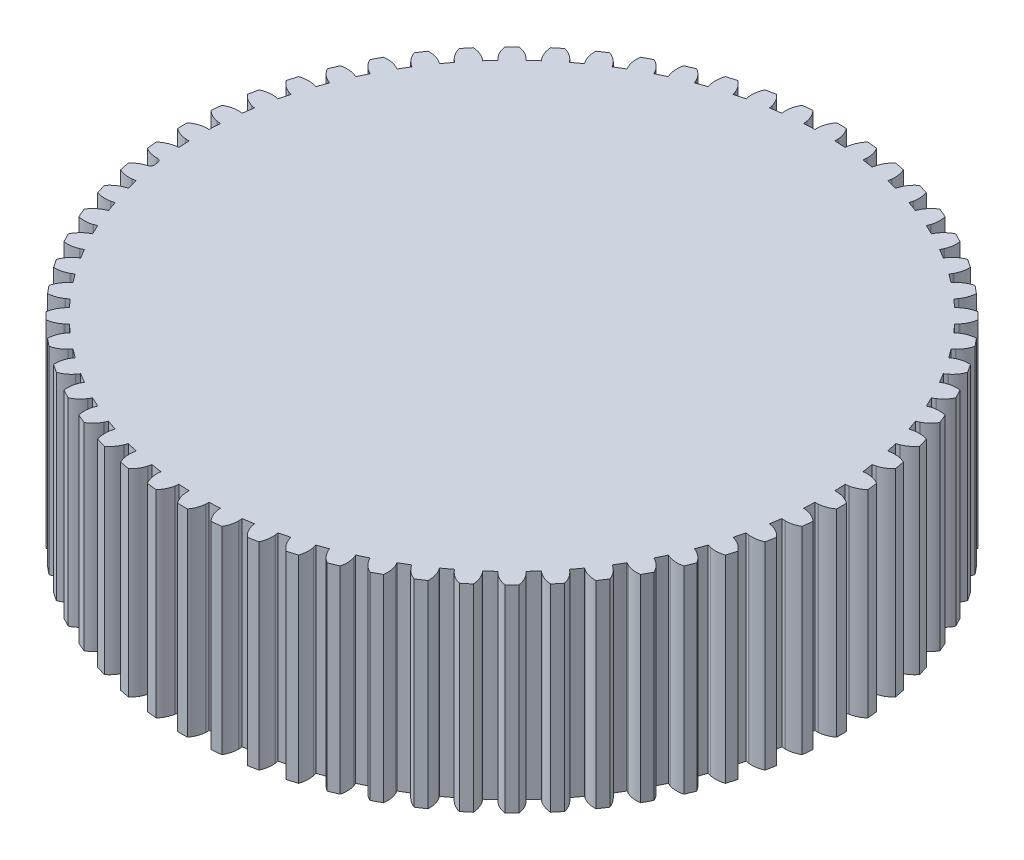
SolidWorks part; units mm, degrees
ref_plane "Front Plane" through (0, 0, 0) normal (0, 0, 1) x (1, 0, 0)
ref_plane "Top Plane" through (0, 0, 0) normal (0, 1, 0) x (1, 0, 0)
ref_plane "Right Plane" through (0, 0, 0) normal (1, 0, 0) x (0, 0, -1)
sketch "Sketch2" plane through (0, 0, 0) normal (0, 1, 0) x (1, 0, 0)
  circle A0 centre (0, 0) radius 47.5
  dimension "D1" = 95
extrude "Boss-Extrude1" add sketch "Sketch2" along normal blind 30
sketch "Sketch3" plane through (0, 30, 0) normal (0, 1, 0) x (1, 0, 0)
  line L0 (0, 0) -> (0, 58.33) construction
  line L1 (-0.75, 49.9944) -> (0.75, 49.9944)
  line L2 (4.1539, 49.8272) -> (5.6467, 49.6801)
  line L3 (9.0178, 49.1801) -> (10.489, 48.8874)
  line L4 (13.7949, 48.0593) -> (15.2303, 47.6239)
  line L5 (18.4391, 46.4758) -> (19.8249, 45.9018)
  line L6 (22.9057, 44.4446) -> (24.2286, 43.7376)
  line L7 (27.1518, 41.9855) -> (28.399, 41.1521)
  line L8 (31.1363, 39.122) -> (32.2959, 38.1704)
  line L9 (34.821, 35.8817) -> (35.8817, 34.821)
  line L10 (38.1704, 32.2959) -> (39.122, 31.1363)
  line L11 (41.1521, 28.399) -> (41.9855, 27.1518)
  line L12 (43.7376, 24.2286) -> (44.4446, 22.9057)
  line L13 (45.9018, 19.8249) -> (46.4758, 18.4391)
  line L14 (47.6239, 15.2303) -> (48.0593, 13.7949)
  line L15 (48.8874, 10.489) -> (49.1801, 9.0178)
  line L16 (49.6801, 5.6467) -> (49.8272, 4.1539)
  line L17 (49.9944, 0.75) -> (49.9944, -0.75)
  line L18 (49.8272, -4.1539) -> (49.6801, -5.6467)
  line L19 (49.1801, -9.0178) -> (48.8874, -10.489)
  line L20 (48.0593, -13.7949) -> (47.6239, -15.2303)
  line L21 (46.4758, -18.4391) -> (45.9018, -19.8249)
  line L22 (44.4446, -22.9057) -> (43.7376, -24.2286)
  line L23 (41.9855, -27.1518) -> (41.1521, -28.399)
  line L24 (39.122, -31.1363) -> (38.1704, -32.2959)
  line L25 (35.8817, -34.821) -> (34.821, -35.8817)
  line L26 (32.2959, -38.1704) -> (31.1363, -39.122)
  line L27 (28.399, -41.1521) -> (27.1518, -41.9855)
  line L28 (24.2286, -43.7376) -> (22.9057, -44.4446)
  line L29 (19.8249, -45.9018) -> (18.4391, -46.4758)
  line L30 (15.2303, -47.6239) -> (13.7949, -48.0593)
  line L31 (10.489, -48.8874) -> (9.0178, -49.1801)
  line L32 (5.6467, -49.6801) -> (4.1539, -49.8272)
  line L33 (0.75, -49.9944) -> (-0.75, -49.9944)
  line L34 (-4.1539, -49.8272) -> (-5.6467, -49.6801)
  line L35 (-9.0178, -49.1801) -> (-10.489, -48.8874)
  line L36 (-13.7949, -48.0593) -> (-15.2303, -47.6239)
  line L37 (-18.4391, -46.4758) -> (-19.8249, -45.9018)
  line L38 (-22.9057, -44.4446) -> (-24.2286, -43.7376)
  line L39 (-27.1518, -41.9855) -> (-28.399, -41.1521)
  line L40 (-31.1363, -39.122) -> (-32.2959, -38.1704)
  line L41 (-34.821, -35.8817) -> (-35.8817, -34.821)
  line L42 (-38.1704, -32.2959) -> (-39.122, -31.1363)
  line L43 (-41.1521, -28.399) -> (-41.9855, -27.1518)
  line L44 (-43.7376, -24.2286) -> (-44.4446, -22.9057)
  line L45 (-45.9018, -19.8249) -> (-46.4758, -18.4391)
  line L46 (-47.6239, -15.2303) -> (-48.0593, -13.7949)
  line L47 (-48.8874, -10.489) -> (-49.1801, -9.0178)
  line L48 (-49.6801, -5.6467) -> (-49.8272, -4.1539)
  line L49 (-49.9944, -0.75) -> (-49.9944, 0.75)
  line L50 (-49.8272, 4.1539) -> (-49.6801, 5.6467)
  line L51 (-49.1801, 9.0178) -> (-48.8874, 10.489)
  line L52 (-48.0593, 13.7949) -> (-47.6239, 15.2303)
  line L53 (-46.4758, 18.4391) -> (-45.9018, 19.8249)
  line L54 (-44.4446, 22.9057) -> (-43.7376, 24.2286)
  line L55 (-41.9855, 27.1518) -> (-41.1521, 28.399)
  line L56 (-39.122, 31.1363) -> (-38.1704, 32.2959)
  line L57 (-35.8817, 34.821) -> (-34.821, 35.8817)
  line L58 (-32.2959, 38.1704) -> (-31.1363, 39.122)
  line L59 (-28.399, 41.1521) -> (-27.1518, 41.9855)
  line L60 (-24.2286, 43.7376) -> (-22.9057, 44.4446)
  line L61 (-19.8249, 45.9018) -> (-18.4391, 46.4758)
  line L62 (-15.2303, 47.6239) -> (-13.7949, 48.0593)
  line L63 (-10.489, 48.8874) -> (-9.0178, 49.1801)
  line L64 (-5.6467, 49.6801) -> (-4.1539, 49.8272)
  circle A0 centre (0, 0) radius 50
  arc A1 (-1.5, 47.3756) -> (-0.75, 49.9944) centre (2.2906, 47.7068) cw
  arc A2 (-2.1047, 47.4533) -> (-1.5, 48.038) centre (-2.0947, 48.048) ccw
  arc A3 (2.1047, 47.4533) -> (1.5, 48.038) centre (2.0947, 48.048) cw
  circle A4 centre (0, 0) radius 47.5 construction
  arc A5 (1.5, 47.3756) -> (0.75, 49.9944) centre (-2.2906, 47.7068) ccw
  arc A6 (3.1508, 47.2945) -> (4.1539, 49.8272) centre (6.9557, 47.2525) cw
  arc A7 (2.5567, 47.4311) -> (3.2158, 47.9537) centre (2.6249, 48.022) ccw
  arc A8 (6.1364, 47.0004) -> (5.6467, 49.6801) centre (2.3965, 47.7016) ccw
  arc A9 (6.7458, 47.0185) -> (6.2013, 47.6596) centre (6.7941, 47.6113) cw
  arc A10 (7.7713, 46.7579) -> (9.0178, 49.1801) centre (11.5537, 46.3432) cw
  arc A11 (7.1934, 46.9522) -> (7.9006, 47.4076) centre (7.3193, 47.5334) ccw
  arc A12 (10.7137, 46.1726) -> (10.489, 48.8874) centre (7.0605, 47.237) ccw
  arc A13 (11.322, 46.1309) -> (10.8429, 46.8223) centre (11.4281, 46.7161) cw
  arc A14 (12.317, 45.771) -> (13.7949, 48.0593) centre (16.0405, 44.9876) cw
  arc A15 (11.7609, 46.021) -> (12.5093, 46.4049) centre (11.9431, 46.5871) ccw
  arc A16 (15.1878, 44.9002) -> (15.2303, 47.6239) centre (11.6566, 46.3175) ccw
  arc A17 (15.7891, 44.7991) -> (15.3801, 45.534) centre (15.9521, 45.371) cw
  arc A18 (16.744, 44.3434) -> (18.4391, 46.4758) centre (20.3729, 43.1987) cw
  arc A19 (16.2151, 44.6466) -> (16.9975, 44.9553) centre (16.452, 45.1922) ccw
  arc A20 (19.5157, 43.1953) -> (19.8249, 45.9018) centre (16.1403, 44.9519) ccw
  arc A21 (20.1041, 43.0357) -> (19.7692, 43.8073) centre (20.3224, 43.589) cw
  arc A22 (21.0098, 42.4886) -> (22.9057, 44.4446) centre (24.509, 40.9938) cw
  arc A23 (20.5132, 42.8423) -> (21.3221, 43.0728) centre (20.8023, 43.362) ccw
  arc A24 (23.6556, 41.0744) -> (24.2286, 43.7376) centre (20.4687, 43.1534) ccw
  arc A25 (24.2256, 40.858) -> (23.9678, 41.6586) centre (24.497, 41.3871) cw
  arc A26 (25.0733, 40.2247) -> (27.1518, 41.9855) centre (28.409, 38.3941) cw
  arc A27 (24.6137, 40.6253) -> (25.4413, 40.7755) centre (24.9524, 41.1142) ccw
  arc A28 (27.5677, 38.558) -> (28.399, 41.1521) centre (24.5999, 40.9393) ccw
  arc A29 (28.1137, 38.2867) -> (27.9357, 39.1087) centre (28.4357, 38.7867) cw
  arc A30 (28.8952, 37.5734) -> (31.1363, 39.122) centre (32.0355, 35.4247) cw
  arc A31 (28.4771, 38.0172) -> (29.3154, 38.0854) centre (28.8621, 38.4705) ccw
  arc A32 (31.2143, 35.6702) -> (32.2959, 38.1704) centre (28.4942, 38.331) ccw
  arc A33 (31.7311, 35.3467) -> (31.6345, 36.1823) centre (32.1005, 35.8128) cw
  arc A34 (32.4389, 34.5603) -> (34.821, 35.8817) centre (35.3535, 32.1141) cw
  arc A35 (32.0663, 35.0428) -> (32.9073, 35.0286) centre (32.4939, 35.4562) ccw
  arc A36 (34.5603, 32.4389) -> (35.8817, 34.821) centre (32.1141, 35.3535) ccw
  arc A37 (35.0428, 32.0663) -> (35.0286, 32.9073) centre (35.4562, 32.4939) cw
  arc A38 (35.6702, 31.2143) -> (38.1704, 32.2959) centre (38.331, 28.4942) cw
  arc A39 (35.3467, 31.7311) -> (36.1823, 31.6345) centre (35.8128, 32.1005) ccw
  arc A40 (37.5734, 28.8952) -> (39.122, 31.1363) centre (35.4247, 32.0355) ccw
  arc A41 (38.0172, 28.4771) -> (38.0854, 29.3154) centre (38.4705, 28.8621) cw
  arc A42 (38.558, 27.5677) -> (41.1521, 28.399) centre (40.9393, 24.5999) cw
  arc A43 (38.2867, 28.1137) -> (39.1087, 27.9357) centre (38.7867, 28.4357) ccw
  arc A44 (40.2247, 25.0733) -> (41.9855, 27.1518) centre (38.3941, 28.409) ccw
  arc A45 (40.6253, 24.6137) -> (40.7755, 25.4413) centre (41.1142, 24.9524) cw
  arc A46 (41.0744, 23.6556) -> (43.7376, 24.2286) centre (43.1534, 20.4687) cw
  arc A47 (40.858, 24.2256) -> (41.6586, 23.9678) centre (41.3871, 24.497) ccw
  arc A48 (42.4886, 21.0098) -> (44.4446, 22.9057) centre (40.9938, 24.509) ccw
  arc A49 (42.8423, 20.5132) -> (43.0728, 21.3221) centre (43.362, 20.8023) cw
  arc A50 (43.1953, 19.5157) -> (45.9018, 19.8249) centre (44.9519, 16.1403) cw
  arc A51 (43.0357, 20.1041) -> (43.8073, 19.7692) centre (43.589, 20.3224) ccw
  arc A52 (44.3434, 16.744) -> (46.4758, 18.4391) centre (43.1987, 20.3729) ccw
  arc A53 (44.6466, 16.2151) -> (44.9553, 16.9975) centre (45.1922, 16.452) cw
  arc A54 (44.9002, 15.1878) -> (47.6239, 15.2303) centre (46.3175, 11.6566) cw
  arc A55 (44.7991, 15.7891) -> (45.534, 15.3801) centre (45.371, 15.9521) ccw
  arc A56 (45.771, 12.317) -> (48.0593, 13.7949) centre (44.9876, 16.0405) ccw
  arc A57 (46.021, 11.7609) -> (46.4049, 12.5093) centre (46.5871, 11.9431) cw
  arc A58 (46.1726, 10.7137) -> (48.8874, 10.489) centre (47.237, 7.0605) cw
  arc A59 (46.1309, 11.322) -> (46.8223, 10.8429) centre (46.7161, 11.4281) ccw
  arc A60 (46.7579, 7.7713) -> (49.1801, 9.0178) centre (46.3432, 11.5537) ccw
  arc A61 (46.9522, 7.1934) -> (47.4076, 7.9006) centre (47.5334, 7.3193) cw
  arc A62 (47.0004, 6.1364) -> (49.6801, 5.6467) centre (47.7016, 2.3965) cw
  arc A63 (47.0185, 6.7458) -> (47.6596, 6.2013) centre (47.6113, 6.7941) ccw
  arc A64 (47.2945, 3.1508) -> (49.8272, 4.1539) centre (47.2525, 6.9557) ccw
  arc A65 (47.4311, 2.5567) -> (47.9537, 3.2158) centre (48.022, 2.6249) cw
  arc A66 (47.3756, 1.5) -> (49.9944, 0.75) centre (47.7068, -2.2906) cw
  arc A67 (47.4533, 2.1047) -> (48.038, 1.5) centre (48.048, 2.0947) ccw
  arc A68 (47.3756, -1.5) -> (49.9944, -0.75) centre (47.7068, 2.2906) ccw
  arc A69 (47.4533, -2.1047) -> (48.038, -1.5) centre (48.048, -2.0947) cw
  arc A70 (47.2945, -3.1508) -> (49.8272, -4.1539) centre (47.2525, -6.9557) cw
  arc A71 (47.4311, -2.5567) -> (47.9537, -3.2158) centre (48.022, -2.6249) ccw
  arc A72 (47.0004, -6.1364) -> (49.6801, -5.6467) centre (47.7016, -2.3965) ccw
  arc A73 (47.0185, -6.7458) -> (47.6596, -6.2013) centre (47.6113, -6.7941) cw
  arc A74 (46.7579, -7.7713) -> (49.1801, -9.0178) centre (46.3432, -11.5537) cw
  arc A75 (46.9522, -7.1934) -> (47.4076, -7.9006) centre (47.5334, -7.3193) ccw
  arc A76 (46.1726, -10.7137) -> (48.8874, -10.489) centre (47.237, -7.0605) ccw
  arc A77 (46.1309, -11.322) -> (46.8223, -10.8429) centre (46.7161, -11.4281) cw
  arc A78 (45.771, -12.317) -> (48.0593, -13.7949) centre (44.9876, -16.0405) cw
  arc A79 (46.021, -11.7609) -> (46.4049, -12.5093) centre (46.5871, -11.9431) ccw
  arc A80 (44.9002, -15.1878) -> (47.6239, -15.2303) centre (46.3175, -11.6566) ccw
  arc A81 (44.7991, -15.7891) -> (45.534, -15.3801) centre (45.371, -15.9521) cw
  arc A82 (44.3434, -16.744) -> (46.4758, -18.4391) centre (43.1987, -20.3729) cw
  arc A83 (44.6466, -16.2151) -> (44.9553, -16.9975) centre (45.1922, -16.452) ccw
  arc A84 (43.1953, -19.5157) -> (45.9018, -19.8249) centre (44.9519, -16.1403) ccw
  arc A85 (43.0357, -20.1041) -> (43.8073, -19.7692) centre (43.589, -20.3224) cw
  arc A86 (42.4886, -21.0098) -> (44.4446, -22.9057) centre (40.9938, -24.509) cw
  arc A87 (42.8423, -20.5132) -> (43.0728, -21.3221) centre (43.362, -20.8023) ccw
  arc A88 (41.0744, -23.6556) -> (43.7376, -24.2286) centre (43.1534, -20.4687) ccw
  arc A89 (40.858, -24.2256) -> (41.6586, -23.9678) centre (41.3871, -24.497) cw
  arc A90 (40.2247, -25.0733) -> (41.9855, -27.1518) centre (38.3941, -28.409) cw
  arc A91 (40.6253, -24.6137) -> (40.7755, -25.4413) centre (41.1142, -24.9524) ccw
  arc A92 (38.558, -27.5677) -> (41.1521, -28.399) centre (40.9393, -24.5999) ccw
  arc A93 (38.2867, -28.1137) -> (39.1087, -27.9357) centre (38.7867, -28.4357) cw
  arc A94 (37.5734, -28.8952) -> (39.122, -31.1363) centre (35.4247, -32.0355) cw
  arc A95 (38.0172, -28.4771) -> (38.0854, -29.3154) centre (38.4705, -28.8621) ccw
  arc A96 (35.6702, -31.2143) -> (38.1704, -32.2959) centre (38.331, -28.4942) ccw
  arc A97 (35.3467, -31.7311) -> (36.1823, -31.6345) centre (35.8128, -32.1005) cw
  arc A98 (34.5603, -32.4389) -> (35.8817, -34.821) centre (32.1141, -35.3535) cw
  arc A99 (35.0428, -32.0663) -> (35.0286, -32.9073) centre (35.4562, -32.4939) ccw
  arc A100 (32.4389, -34.5603) -> (34.821, -35.8817) centre (35.3535, -32.1141) ccw
  arc A101 (32.0663, -35.0428) -> (32.9073, -35.0286) centre (32.4939, -35.4562) cw
  arc A102 (31.2143, -35.6702) -> (32.2959, -38.1704) centre (28.4942, -38.331) cw
  arc A103 (31.7311, -35.3467) -> (31.6345, -36.1823) centre (32.1005, -35.8128) ccw
  arc A104 (28.8952, -37.5734) -> (31.1363, -39.122) centre (32.0355, -35.4247) ccw
  arc A105 (28.4771, -38.0172) -> (29.3154, -38.0854) centre (28.8621, -38.4705) cw
  arc A106 (27.5677, -38.558) -> (28.399, -41.1521) centre (24.5999, -40.9393) cw
  arc A107 (28.1137, -38.2867) -> (27.9357, -39.1087) centre (28.4357, -38.7867) ccw
  arc A108 (25.0733, -40.2247) -> (27.1518, -41.9855) centre (28.409, -38.3941) ccw
  arc A109 (24.6137, -40.6253) -> (25.4413, -40.7755) centre (24.9524, -41.1142) cw
  arc A110 (23.6556, -41.0744) -> (24.2286, -43.7376) centre (20.4687, -43.1534) cw
  arc A111 (24.2256, -40.858) -> (23.9678, -41.6586) centre (24.497, -41.3871) ccw
  arc A112 (21.0098, -42.4886) -> (22.9057, -44.4446) centre (24.509, -40.9938) ccw
  arc A113 (20.5132, -42.8423) -> (21.3221, -43.0728) centre (20.8023, -43.362) cw
  arc A114 (19.5157, -43.1953) -> (19.8249, -45.9018) centre (16.1403, -44.9519) cw
  arc A115 (20.1041, -43.0357) -> (19.7692, -43.8073) centre (20.3224, -43.589) ccw
  arc A116 (16.744, -44.3434) -> (18.4391, -46.4758) centre (20.3729, -43.1987) ccw
  arc A117 (16.2151, -44.6466) -> (16.9975, -44.9553) centre (16.452, -45.1922) cw
  arc A118 (15.1878, -44.9002) -> (15.2303, -47.6239) centre (11.6566, -46.3175) cw
  arc A119 (15.7891, -44.7991) -> (15.3801, -45.534) centre (15.9521, -45.371) ccw
  arc A120 (12.317, -45.771) -> (13.7949, -48.0593) centre (16.0405, -44.9876) ccw
  arc A121 (11.7609, -46.021) -> (12.5093, -46.4049) centre (11.9431, -46.5871) cw
  arc A122 (10.7137, -46.1726) -> (10.489, -48.8874) centre (7.0605, -47.237) cw
  arc A123 (11.322, -46.1309) -> (10.8429, -46.8223) centre (11.4281, -46.7161) ccw
  arc A124 (7.7713, -46.7579) -> (9.0178, -49.1801) centre (11.5537, -46.3432) ccw
  arc A125 (7.1934, -46.9522) -> (7.9006, -47.4076) centre (7.3193, -47.5334) cw
  arc A126 (6.1364, -47.0004) -> (5.6467, -49.6801) centre (2.3965, -47.7016) cw
  arc A127 (6.7458, -47.0185) -> (6.2013, -47.6596) centre (6.7941, -47.6113) ccw
  arc A128 (3.1508, -47.2945) -> (4.1539, -49.8272) centre (6.9557, -47.2525) ccw
  arc A129 (2.5567, -47.4311) -> (3.2158, -47.9537) centre (2.6249, -48.022) cw
  arc A130 (1.5, -47.3756) -> (0.75, -49.9944) centre (-2.2906, -47.7068) cw
  arc A131 (2.1047, -47.4533) -> (1.5, -48.038) centre (2.0947, -48.048) ccw
  arc A132 (-1.5, -47.3756) -> (-0.75, -49.9944) centre (2.2906, -47.7068) ccw
  arc A133 (-2.1047, -47.4533) -> (-1.5, -48.038) centre (-2.0947, -48.048) cw
  arc A134 (-3.1508, -47.2945) -> (-4.1539, -49.8272) centre (-6.9557, -47.2525) cw
  arc A135 (-2.5567, -47.4311) -> (-3.2158, -47.9537) centre (-2.6249, -48.022) ccw
  arc A136 (-6.1364, -47.0004) -> (-5.6467, -49.6801) centre (-2.3965, -47.7016) ccw
  arc A137 (-6.7458, -47.0185) -> (-6.2013, -47.6596) centre (-6.7941, -47.6113) cw
  arc A138 (-7.7713, -46.7579) -> (-9.0178, -49.1801) centre (-11.5537, -46.3432) cw
  arc A139 (-7.1934, -46.9522) -> (-7.9006, -47.4076) centre (-7.3193, -47.5334) ccw
  arc A140 (-10.7137, -46.1726) -> (-10.489, -48.8874) centre (-7.0605, -47.237) ccw
  arc A141 (-11.322, -46.1309) -> (-10.8429, -46.8223) centre (-11.4281, -46.7161) cw
  arc A142 (-12.317, -45.771) -> (-13.7949, -48.0593) centre (-16.0405, -44.9876) cw
  arc A143 (-11.7609, -46.021) -> (-12.5093, -46.4049) centre (-11.9431, -46.5871) ccw
  arc A144 (-15.1878, -44.9002) -> (-15.2303, -47.6239) centre (-11.6566, -46.3175) ccw
  arc A145 (-15.7891, -44.7991) -> (-15.3801, -45.534) centre (-15.9521, -45.371) cw
  arc A146 (-16.744, -44.3434) -> (-18.4391, -46.4758) centre (-20.3729, -43.1987) cw
  arc A147 (-16.2151, -44.6466) -> (-16.9975, -44.9553) centre (-16.452, -45.1922) ccw
  arc A148 (-19.5157, -43.1953) -> (-19.8249, -45.9018) centre (-16.1403, -44.9519) ccw
  arc A149 (-20.1041, -43.0357) -> (-19.7692, -43.8073) centre (-20.3224, -43.589) cw
  arc A150 (-21.0098, -42.4886) -> (-22.9057, -44.4446) centre (-24.509, -40.9938) cw
  arc A151 (-20.5132, -42.8423) -> (-21.3221, -43.0728) centre (-20.8023, -43.362) ccw
  arc A152 (-23.6556, -41.0744) -> (-24.2286, -43.7376) centre (-20.4687, -43.1534) ccw
  arc A153 (-24.2256, -40.858) -> (-23.9678, -41.6586) centre (-24.497, -41.3871) cw
  arc A154 (-25.0733, -40.2247) -> (-27.1518, -41.9855) centre (-28.409, -38.3941) cw
  arc A155 (-24.6137, -40.6253) -> (-25.4413, -40.7755) centre (-24.9524, -41.1142) ccw
  arc A156 (-27.5677, -38.558) -> (-28.399, -41.1521) centre (-24.5999, -40.9393) ccw
  arc A157 (-28.1137, -38.2867) -> (-27.9357, -39.1087) centre (-28.4357, -38.7867) cw
  arc A158 (-28.8952, -37.5734) -> (-31.1363, -39.122) centre (-32.0355, -35.4247) cw
  arc A159 (-28.4771, -38.0172) -> (-29.3154, -38.0854) centre (-28.8621, -38.4705) ccw
  arc A160 (-31.2143, -35.6702) -> (-32.2959, -38.1704) centre (-28.4942, -38.331) ccw
  arc A161 (-31.7311, -35.3467) -> (-31.6345, -36.1823) centre (-32.1005, -35.8128) cw
  arc A162 (-32.4389, -34.5603) -> (-34.821, -35.8817) centre (-35.3535, -32.1141) cw
  arc A163 (-32.0663, -35.0428) -> (-32.9073, -35.0286) centre (-32.4939, -35.4562) ccw
  arc A164 (-34.5603, -32.4389) -> (-35.8817, -34.821) centre (-32.1141, -35.3535) ccw
  arc A165 (-35.0428, -32.0663) -> (-35.0286, -32.9073) centre (-35.4562, -32.4939) cw
  arc A166 (-35.6702, -31.2143) -> (-38.1704, -32.2959) centre (-38.331, -28.4942) cw
  arc A167 (-35.3467, -31.7311) -> (-36.1823, -31.6345) centre (-35.8128, -32.1005) ccw
  arc A168 (-37.5734, -28.8952) -> (-39.122, -31.1363) centre (-35.4247, -32.0355) ccw
  arc A169 (-38.0172, -28.4771) -> (-38.0854, -29.3154) centre (-38.4705, -28.8621) cw
  arc A170 (-38.558, -27.5677) -> (-41.1521, -28.399) centre (-40.9393, -24.5999) cw
  arc A171 (-38.2867, -28.1137) -> (-39.1087, -27.9357) centre (-38.7867, -28.4357) ccw
  arc A172 (-40.2247, -25.0733) -> (-41.9855, -27.1518) centre (-38.3941, -28.409) ccw
  arc A173 (-40.6253, -24.6137) -> (-40.7755, -25.4413) centre (-41.1142, -24.9524) cw
  arc A174 (-41.0744, -23.6556) -> (-43.7376, -24.2286) centre (-43.1534, -20.4687) cw
  arc A175 (-40.858, -24.2256) -> (-41.6586, -23.9678) centre (-41.3871, -24.497) ccw
  arc A176 (-42.4886, -21.0098) -> (-44.4446, -22.9057) centre (-40.9938, -24.509) ccw
  arc A177 (-42.8423, -20.5132) -> (-43.0728, -21.3221) centre (-43.362, -20.8023) cw
  arc A178 (-43.1953, -19.5157) -> (-45.9018, -19.8249) centre (-44.9519, -16.1403) cw
  arc A179 (-43.0357, -20.1041) -> (-43.8073, -19.7692) centre (-43.589, -20.3224) ccw
  arc A180 (-44.3434, -16.744) -> (-46.4758, -18.4391) centre (-43.1987, -20.3729) ccw
  arc A181 (-44.6466, -16.2151) -> (-44.9553, -16.9975) centre (-45.1922, -16.452) cw
  arc A182 (-44.9002, -15.1878) -> (-47.6239, -15.2303) centre (-46.3175, -11.6566) cw
  arc A183 (-44.7991, -15.7891) -> (-45.534, -15.3801) centre (-45.371, -15.9521) ccw
  arc A184 (-45.771, -12.317) -> (-48.0593, -13.7949) centre (-44.9876, -16.0405) ccw
  arc A185 (-46.021, -11.7609) -> (-46.4049, -12.5093) centre (-46.5871, -11.9431) cw
  arc A186 (-46.1726, -10.7137) -> (-48.8874, -10.489) centre (-47.237, -7.0605) cw
  arc A187 (-46.1309, -11.322) -> (-46.8223, -10.8429) centre (-46.7161, -11.4281) ccw
  arc A188 (-46.7579, -7.7713) -> (-49.1801, -9.0178) centre (-46.3432, -11.5537) ccw
  arc A189 (-46.9522, -7.1934) -> (-47.4076, -7.9006) centre (-47.5334, -7.3193) cw
  arc A190 (-47.0004, -6.1364) -> (-49.6801, -5.6467) centre (-47.7016, -2.3965) cw
  arc A191 (-47.0185, -6.7458) -> (-47.6596, -6.2013) centre (-47.6113, -6.7941) ccw
  arc A192 (-47.2945, -3.1508) -> (-49.8272, -4.1539) centre (-47.2525, -6.9557) ccw
  arc A193 (-47.4311, -2.5567) -> (-47.9537, -3.2158) centre (-48.022, -2.6249) cw
  arc A194 (-47.3756, -1.5) -> (-49.9944, -0.75) centre (-47.7068, 2.2906) cw
  arc A195 (-47.4533, -2.1047) -> (-48.038, -1.5) centre (-48.048, -2.0947) ccw
  arc A196 (-47.3756, 1.5) -> (-49.9944, 0.75) centre (-47.7068, -2.2906) ccw
  arc A197 (-47.4533, 2.1047) -> (-48.038, 1.5) centre (-48.048, 2.0947) cw
  arc A198 (-47.2945, 3.1508) -> (-49.8272, 4.1539) centre (-47.2525, 6.9557) cw
  arc A199 (-47.4311, 2.5567) -> (-47.9537, 3.2158) centre (-48.022, 2.6249) ccw
  arc A200 (-47.0004, 6.1364) -> (-49.6801, 5.6467) centre (-47.7016, 2.3965) ccw
  arc A201 (-47.0185, 6.7458) -> (-47.6596, 6.2013) centre (-47.6113, 6.7941) cw
  arc A202 (-46.7579, 7.7713) -> (-49.1801, 9.0178) centre (-46.3432, 11.5537) cw
  arc A203 (-46.9522, 7.1934) -> (-47.4076, 7.9006) centre (-47.5334, 7.3193) ccw
  arc A204 (-46.1726, 10.7137) -> (-48.8874, 10.489) centre (-47.237, 7.0605) ccw
  arc A205 (-46.1309, 11.322) -> (-46.8223, 10.8429) centre (-46.7161, 11.4281) cw
  arc A206 (-45.771, 12.317) -> (-48.0593, 13.7949) centre (-44.9876, 16.0405) cw
  arc A207 (-46.021, 11.7609) -> (-46.4049, 12.5093) centre (-46.5871, 11.9431) ccw
  arc A208 (-44.9002, 15.1878) -> (-47.6239, 15.2303) centre (-46.3175, 11.6566) ccw
  arc A209 (-44.7991, 15.7891) -> (-45.534, 15.3801) centre (-45.371, 15.9521) cw
  arc A210 (-44.3434, 16.744) -> (-46.4758, 18.4391) centre (-43.1987, 20.3729) cw
  arc A211 (-44.6466, 16.2151) -> (-44.9553, 16.9975) centre (-45.1922, 16.452) ccw
  arc A212 (-43.1953, 19.5157) -> (-45.9018, 19.8249) centre (-44.9519, 16.1403) ccw
  arc A213 (-43.0357, 20.1041) -> (-43.8073, 19.7692) centre (-43.589, 20.3224) cw
  arc A214 (-42.4886, 21.0098) -> (-44.4446, 22.9057) centre (-40.9938, 24.509) cw
  arc A215 (-42.8423, 20.5132) -> (-43.0728, 21.3221) centre (-43.362, 20.8023) ccw
  arc A216 (-41.0744, 23.6556) -> (-43.7376, 24.2286) centre (-43.1534, 20.4687) ccw
  arc A217 (-40.858, 24.2256) -> (-41.6586, 23.9678) centre (-41.3871, 24.497) cw
  arc A218 (-40.2247, 25.0733) -> (-41.9855, 27.1518) centre (-38.3941, 28.409) cw
  arc A219 (-40.6253, 24.6137) -> (-40.7755, 25.4413) centre (-41.1142, 24.9524) ccw
  arc A220 (-38.558, 27.5677) -> (-41.1521, 28.399) centre (-40.9393, 24.5999) ccw
  arc A221 (-38.2867, 28.1137) -> (-39.1087, 27.9357) centre (-38.7867, 28.4357) cw
  arc A222 (-37.5734, 28.8952) -> (-39.122, 31.1363) centre (-35.4247, 32.0355) cw
  arc A223 (-38.0172, 28.4771) -> (-38.0854, 29.3154) centre (-38.4705, 28.8621) ccw
  arc A224 (-35.6702, 31.2143) -> (-38.1704, 32.2959) centre (-38.331, 28.4942) ccw
  arc A225 (-35.3467, 31.7311) -> (-36.1823, 31.6345) centre (-35.8128, 32.1005) cw
  arc A226 (-34.5603, 32.4389) -> (-35.8817, 34.821) centre (-32.1141, 35.3535) cw
  arc A227 (-35.0428, 32.0663) -> (-35.0286, 32.9073) centre (-35.4562, 32.4939) ccw
  arc A228 (-32.4389, 34.5603) -> (-34.821, 35.8817) centre (-35.3535, 32.1141) ccw
  arc A229 (-32.0663, 35.0428) -> (-32.9073, 35.0286) centre (-32.4939, 35.4562) cw
  arc A230 (-31.2143, 35.6702) -> (-32.2959, 38.1704) centre (-28.4942, 38.331) cw
  arc A231 (-31.7311, 35.3467) -> (-31.6345, 36.1823) centre (-32.1005, 35.8128) ccw
  arc A232 (-28.8952, 37.5734) -> (-31.1363, 39.122) centre (-32.0355, 35.4247) ccw
  arc A233 (-28.4771, 38.0172) -> (-29.3154, 38.0854) centre (-28.8621, 38.4705) cw
  arc A234 (-27.5677, 38.558) -> (-28.399, 41.1521) centre (-24.5999, 40.9393) cw
  arc A235 (-28.1137, 38.2867) -> (-27.9357, 39.1087) centre (-28.4357, 38.7867) ccw
  arc A236 (-25.0733, 40.2247) -> (-27.1518, 41.9855) centre (-28.409, 38.3941) ccw
  arc A237 (-24.6137, 40.6253) -> (-25.4413, 40.7755) centre (-24.9524, 41.1142) cw
  arc A238 (-23.6556, 41.0744) -> (-24.2286, 43.7376) centre (-20.4687, 43.1534) cw
  arc A239 (-24.2256, 40.858) -> (-23.9678, 41.6586) centre (-24.497, 41.3871) ccw
  arc A240 (-21.0098, 42.4886) -> (-22.9057, 44.4446) centre (-24.509, 40.9938) ccw
  arc A241 (-20.5132, 42.8423) -> (-21.3221, 43.0728) centre (-20.8023, 43.362) cw
  arc A242 (-19.5157, 43.1953) -> (-19.8249, 45.9018) centre (-16.1403, 44.9519) cw
  arc A243 (-20.1041, 43.0357) -> (-19.7692, 43.8073) centre (-20.3224, 43.589) ccw
  arc A244 (-16.744, 44.3434) -> (-18.4391, 46.4758) centre (-20.3729, 43.1987) ccw
  arc A245 (-16.2151, 44.6466) -> (-16.9975, 44.9553) centre (-16.452, 45.1922) cw
  arc A246 (-15.1878, 44.9002) -> (-15.2303, 47.6239) centre (-11.6566, 46.3175) cw
  arc A247 (-15.7891, 44.7991) -> (-15.3801, 45.534) centre (-15.9521, 45.371) ccw
  arc A248 (-12.317, 45.771) -> (-13.7949, 48.0593) centre (-16.0405, 44.9876) ccw
  arc A249 (-11.7609, 46.021) -> (-12.5093, 46.4049) centre (-11.9431, 46.5871) cw
  arc A250 (-10.7137, 46.1726) -> (-10.489, 48.8874) centre (-7.0605, 47.237) cw
  arc A251 (-11.322, 46.1309) -> (-10.8429, 46.8223) centre (-11.4281, 46.7161) ccw
  arc A252 (-7.7713, 46.7579) -> (-9.0178, 49.1801) centre (-11.5537, 46.3432) ccw
  arc A253 (-7.1934, 46.9522) -> (-7.9006, 47.4076) centre (-7.3193, 47.5334) cw
  arc A254 (-6.1364, 47.0004) -> (-5.6467, 49.6801) centre (-2.3965, 47.7016) cw
  arc A255 (-6.7458, 47.0185) -> (-6.2013, 47.6596) centre (-6.7941, 47.6113) ccw
  arc A256 (-3.1508, 47.2945) -> (-4.1539, 49.8272) centre (-6.9557, 47.2525) ccw
  arc A257 (-2.5567, 47.4311) -> (-3.2158, 47.9537) centre (-2.6249, 48.022) cw
  point P777 (0, 0)
  circle M3 centre (0, 0) radius 47.5
  dimension "D1" = 100
  dimension "D2" = 0.75
  dimension "D3" = 1.5
  dimension "D4" = 64
extrude "Boss-Extrude2" add sketch "Sketch3" against normal blind 30 contours A192 A193 L48 A190 A191 M3 | A196 A197 L49 A194 A195 M3 | A188 A189 L47 A186 A187 M3 | A191 A190 M3 | A189 A188 M3 | A184 A185 L46 A182 A183 M3 | A180 A181 L45 A178 A179 M3 | A176 A177 L44 A174 A175 M3 | A172 A173 L43 A170 A171 M3 | A168 A169 L42 A166 A167 M3 | A164 A165 L41 A162 A163 M3 | A160 A161 L40 A158 A159 M3 | A156 A157 L39 A154 A155 M3 | A152 A153 L38 A150 A151 M3 | A148 A149 L37 A146 A147 M3 | A144 A145 L36 A142 A143 M3 | A140 A141 L35 A138 A139 M3 | A136 A137 L34 A134 A135 M3 | A132 A133 L33 A130 A131 M3 | A128 A129 L32 A126 A127 M3 | A124 A125 L31 A122 A123 M3 | A120 A121 L30 A118 A119 M3 | A116 A117 L29 A114 A115 M3 | A112 A113 L28 A110 A111 M3 | A108 A109 L27 A106 A107 M3 | A104 A105 L26 A102 A103 M3 | A100 A101 L25 A98 A99 M3 | A96 A97 L24 A94 A95 M3 | A92 A93 L23 A90 A91 M3 | A88 A89 L22 A86 A87 M3 | A84 A85 L21 A82 A83 M3 | A80 A81 L20 A78 A79 M3 | A76 A77 L19 A74 A75 M3 | A72 A73 L18 A70 A71 M3 | A68 A69 L17 A66 A67 M3 | A64 A65 L16 A62 A63 M3 | A60 A61 L15 A58 A59 M3 | A56 A57 L14 A54 A55 M3 | A52 A53 L13 A50 A51 M3 | A48 A49 L12 A46 A47 M3 | A44 A45 L11 A42 A43 M3 | A36 A37 L9 A34 A35 M3 | A40 A41 L10 A38 A39 M3 | A32 A33 L8 A30 A31 M3 | A28 A29 L7 A26 A27 M3 | A24 A25 L6 A22 A23 M3 | A20 A21 L5 A18 A19 M3 | A16 A17 L4 A14 A15 M3 | A12 A13 L3 A10 A11 M3 | A8 A9 L2 A6 A7 M3 | L0 A5 A3 L1 M3 | L0 L1 A1 A2 M3 | A256 A257 L64 A254 A255 M3 | A200 A201 L50 A198 A199 M3 | A204 A205 L51 A202 A203 M3 | A208 A209 L52 A206 A207 M3 | A212 A213 L53 A210 A211 M3 | A216 A217 L54 A214 A215 M3 | A220 A221 L55 A218 A219 M3 | A224 A225 L56 A222 A223 M3 | A228 A229 L57 A226 A227 M3 | A232 A233 L58 A230 A231 M3 | A236 A237 L59 A234 A235 M3 | A240 A241 L60 A238 A239 M3 | A244 A245 L61 A242 A243 M3 | A248 A249 L62 A246 A247 M3 | A252 A253 L63 A250 A251 M3 region at (-0.6667, 30, -48.6241) region at (0.6667, 30, -48.6241) region at (-4.766, 30, -48.39) region at (4.766, 30, -48.39) region at (-9.4861, 30, -47.6898) region at (9.4861, 30, -47.6898) region at (-14.1148, 30, -46.5304) region at (14.1148, 30, -46.5304) region at (-18.6077, 30, -44.9228) region at (18.6077, 30, -44.9228) region at (-22.9213, 30, -42.8827) region at (22.9213, 30, -42.8827) region at (-27.0141, 30, -40.4295) region at (27.0141, 30, -40.4295) region at (-30.8468, 30, -37.587) region at (30.8468, 30, -37.587) region at (-34.3825, 30, -34.3825) region at (34.3825, 30, -34.3825) region at (-37.587, 30, -30.8468) region at (37.587, 30, -30.8468) region at (-40.4295, 30, -27.0141) region at (40.4295, 30, -27.0141) region at (-42.8827, 30, -22.9213) region at (42.8827, 30, -22.9213) region at (-44.9228, 30, -18.6077) region at (44.9228, 30, -18.6077) region at (-46.5304, 30, -14.1148) region at (46.5304, 30, -14.1148) region at (-47.6898, 30, -9.4861) region at (47.6898, 30, -9.4861) region at (-48.39, 30, -4.766) region at (48.39, 30, -4.766) region at (-48.6241, 30, 0) region at (48.6241, 30, 0) region at (-48.39, 30, 4.766) region at (48.39, 30, 4.766) region at (-47.6898, 30, 9.4861) region at (47.6898, 30, 9.4861) region at (-47.1983, 30, 6.2929) region at (-46.5304, 30, 14.1148) region at (-46.9927, 30, 7.679) region at (46.5304, 30, 14.1148) region at (-44.9228, 30, 18.6077) region at (44.9228, 30, 18.6077) region at (-42.8827, 30, 22.9213) region at (42.8827, 30, 22.9213) region at (-40.4295, 30, 27.0141) region at (40.4295, 30, 27.0141) region at (-37.587, 30, 30.8468) region at (37.587, 30, 30.8468) region at (-34.3825, 30, 34.3825) region at (34.3825, 30, 34.3825) region at (-30.8468, 30, 37.587) region at (30.8468, 30, 37.587) region at (-27.0141, 30, 40.4295) region at (27.0141, 30, 40.4295) region at (-22.9213, 30, 42.8827) region at (22.9213, 30, 42.8827) region at (-18.6077, 30, 44.9228) region at (18.6077, 30, 44.9228)
